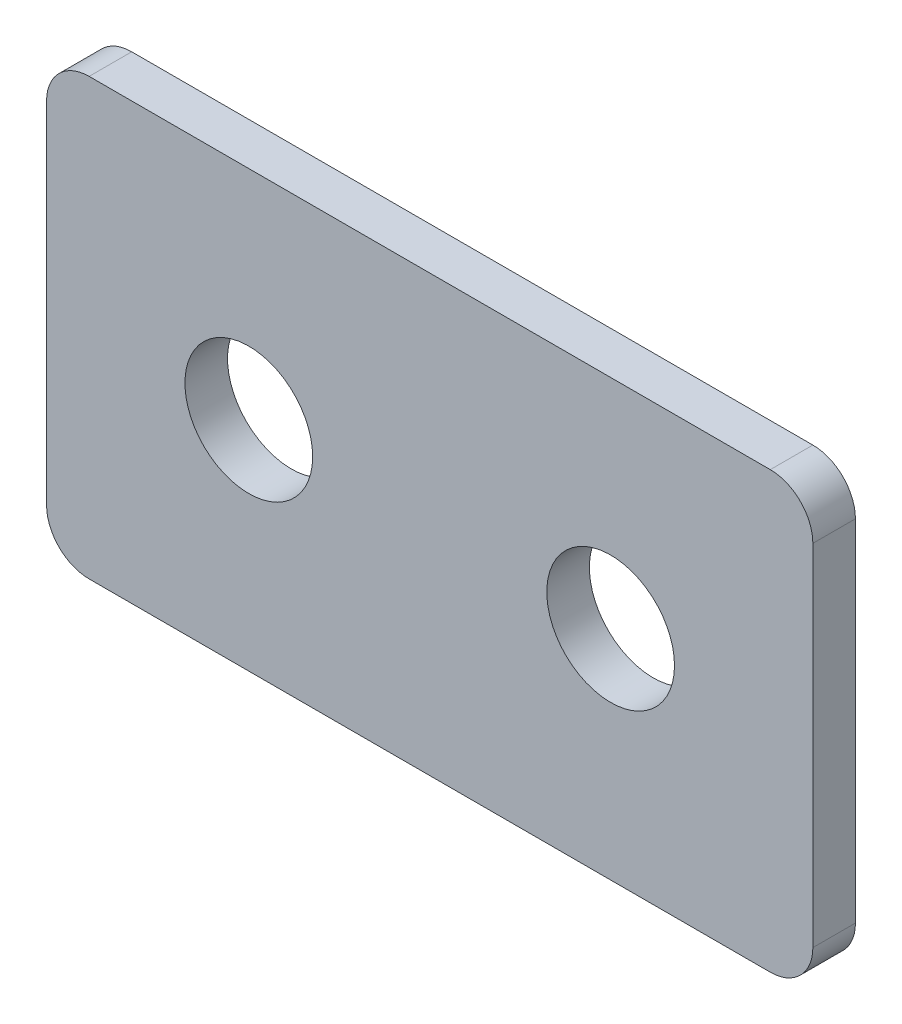
SolidWorks part; units mm, degrees
ref_plane "Front Plane" through (0, 0, 0) normal (0, 0, 1) x (1, 0, 0)
ref_plane "Top Plane" through (0, 0, 0) normal (0, 1, 0) x (1, 0, 0)
ref_plane "Right Plane" through (0, 0, 0) normal (1, 0, 0) x (0, 0, -1)
sketch "Sketch1" plane through (0, 0, 0) normal (0, 0, 1) x (1, 0, 0)
  line L0 (0, 0) -> (26.9875, 0) construction
  line L2 (38.8937, -16.2306) -> (-11.9062, -16.2306)
  line L3 (42.0687, -13.0556) -> (42.0687, 13.0556)
  line L4 (38.8937, 16.2306) -> (-11.9062, 16.2306)
  line L5 (-15.0813, -13.0556) -> (-15.0813, 13.0556)
  line L6 (42.0687, -16.2306) -> (-15.0813, 16.2306) construction
  line L7 (42.0687, 16.2306) -> (-15.0813, -16.2306) construction
  circle A0 centre (0, 0) radius 4.7625
  circle A1 centre (26.9875, 0) radius 4.7625
  arc A2 (42.0687, 13.0556) -> (38.8937, 16.2306) centre (38.8937, 13.0556) ccw
  arc A3 (38.8937, -16.2306) -> (42.0687, -13.0556) centre (38.8937, -13.0556) ccw
  arc A4 (-11.9062, -16.2306) -> (-15.0813, -13.0556) centre (-11.9063, -13.0556) cw
  arc A5 (-11.9062, 16.2306) -> (-15.0813, 13.0556) centre (-11.9063, 13.0556) ccw
  point P5 (13.4937, 0)
  dimension "D1" = 9.525
  dimension "D2" = 26.9875
  dimension "D5" = 3.175
  dimension "D3" = 32.4612
  dimension "D4" = 57.15
extrude "Boss-Extrude1" add sketch "Sketch1" along normal blind 3.175
